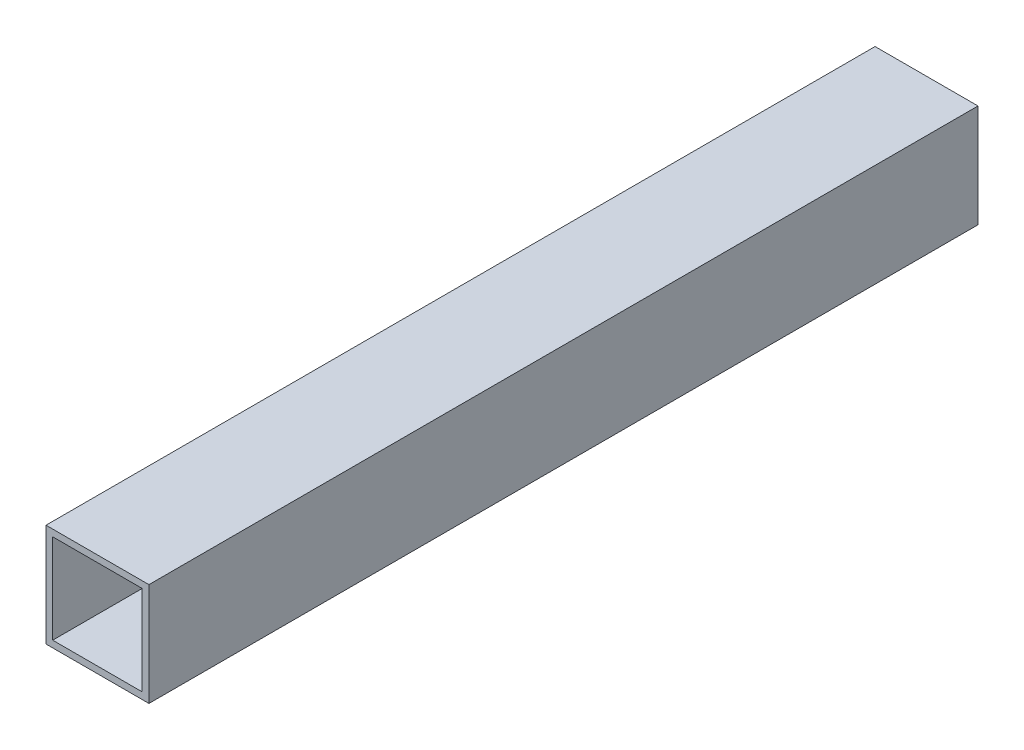
SolidWorks part; units mm, degrees
ref_plane "Front Plane" through (0, 0, 0) normal (0, 0, 1) x (1, 0, 0)
ref_plane "Top Plane" through (0, 0, 0) normal (0, 1, 0) x (1, 0, 0)
ref_plane "Right Plane" through (0, 0, 0) normal (1, 0, 0) x (0, 0, -1)
sketch "Sketch1" plane through (0, 0, 0) normal (0, 0, 1) x (1, 0, 0)
  line L1 (0, 0) -> (25.4, 0)
  line L2 (0, 0) -> (0, 25.4)
  line L3 (0, 25.4) -> (25.4, 25.4)
  line L4 (25.4, 0) -> (25.4, 25.4)
  dimension "D1" = 25.4
  dimension "D2" = 25.4
extrude "Boss-Extrude1" add sketch "Sketch1" along normal blind 204.6
shell "Shell1" thickness 1.651 removed face at (12.7, 12.7, 204.6) removed face at (12.7, 12.7, 0)
equation "\"ExtrusionLen\"= 204.60"
equation "\"D1@Boss-Extrude1\"=\"ExtrusionLen\""
